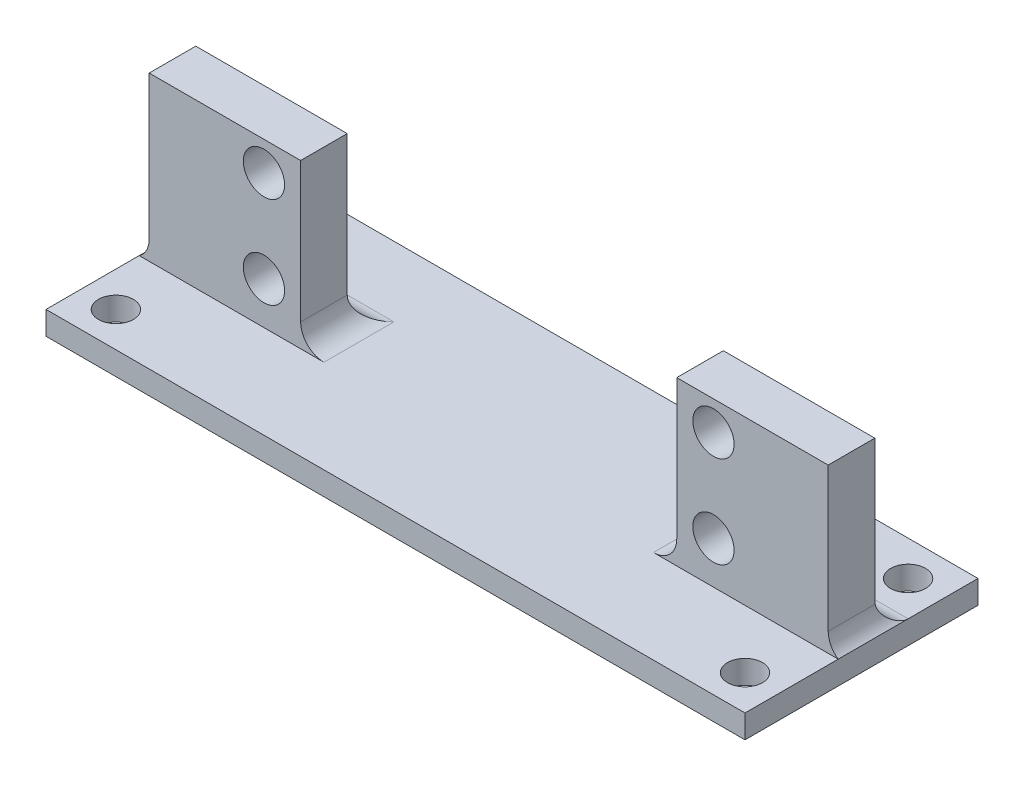
SolidWorks part; units mm, degrees
ref_plane "Front Plane" through (0, 0, 0) normal (0, 0, 1) x (1, 0, 0)
ref_plane "Top Plane" through (0, 0, 0) normal (0, 1, 0) x (1, 0, 0)
ref_plane "Right Plane" through (0, 0, 0) normal (1, 0, 0) x (0, 0, -1)
sketch "Sketch1" plane through (0, 0, 0) normal (0, 1, 0) x (1, 0, 0)
  line L1 (-38.1, 12.7) -> (38.1, 12.7)
  line L2 (-38.1, 12.7) -> (-38.1, -12.7)
  line L3 (-38.1, -12.7) -> (38.1, -12.7)
  line L4 (38.1, 12.7) -> (38.1, -12.7)
  line L5 (-38.1, 12.7) -> (38.1, -12.7) construction
  line L6 (-38.1, -12.7) -> (38.1, 12.7) construction
  circle A0 centre (-34.29, 8.89) radius 1.905
  circle A1 centre (-34.29, -8.89) radius 1.905
  circle A2 centre (34.29, 8.89) radius 1.905
  circle A3 centre (34.29, -8.89) radius 1.905
  point P0 (0, 0)
  dimension "D3" = 3.81
  dimension "D6" = 3.81
  dimension "D1" = 76.2
  dimension "D2" = 25.4
  dimension "D4" = 3.81
  dimension "D5" = 3.81
  dimension "D7" = 3.81
extrude "Boss-Extrude1" add sketch "Sketch1" along normal blind 2.54
sketch "Sketch2" plane through (0, 2.54, 0) normal (0, 1, 0) x (1, 0, 0)
  line L0 (-20.5, 0) -> (20.5, 0) construction
  line L1 (-37.01, 2.54) -> (-20.5, 2.54)
  line L2 (-37.01, 2.54) -> (-37.01, -2.54)
  line L3 (-37.01, -2.54) -> (-20.5, -2.54)
  line L4 (-20.5, 2.54) -> (-20.5, -2.54)
  line L5 (20.5, 2.54) -> (37.01, 2.54)
  line L6 (20.5, 2.54) -> (20.5, -2.54)
  line L7 (20.5, -2.54) -> (37.01, -2.54)
  line L8 (37.01, 2.54) -> (37.01, -2.54)
  point P10 (0, 0)
  dimension "D1" = 16.51
  dimension "D2" = 5.08
  dimension "D3" = 41
  dimension "D4" = 0
extrude "Boss-Extrude2" add sketch "Sketch2" along normal blind 17.78
sketch "Sketch3" plane through (0, 0, 2.54) normal (0, 0, 1) x (1, 0, 0)
  line L0 (-24.5, 17.14) -> (24.5, 17.14) construction
  line L1 (-37.01, 2.54) -> (-20.5, 2.54) construction
  circle A0 centre (-24.5, 17.14) radius 2.25
  circle A1 centre (24.5, 17.14) radius 2.25
  circle A2 centre (-24.5, 7.14) radius 2.25
  circle A3 centre (24.5, 7.14) radius 2.25
  point P8 (0, 17.14)
  dimension "D2" = 4.5
  dimension "D1" = 49
  dimension "D3" = 10
  dimension "D4" = 4.6
extrude "Cut-Extrude1" cut sketch "Sketch3" against normal through all
fillet "Fillet1" radius 2.54 6 edges at (-20.5, 2.54, 0) (-28.755, 2.54, -2.54) (-37.01, 2.54, 0) (37.01, 2.54, 0) (20.5, 2.54, 0) (28.755, 2.54, -2.54)
